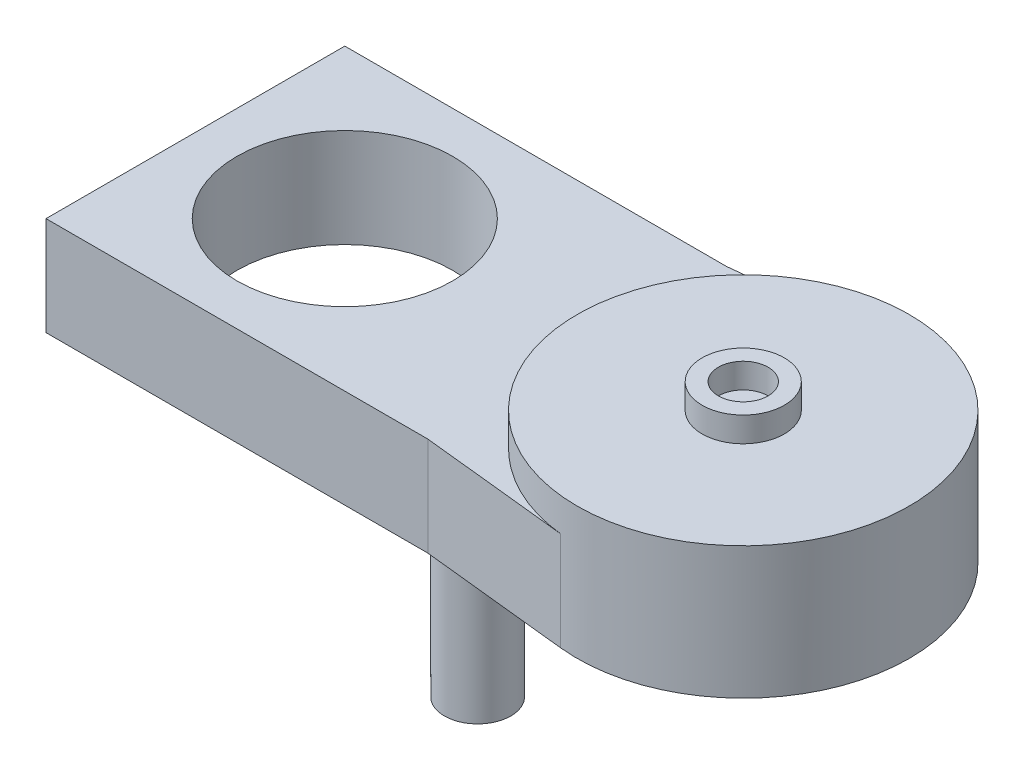
SolidWorks part; units mm, degrees
ref_plane "Front Plane" through (0, 0, 0) normal (0, 0, 1) x (1, 0, 0)
ref_plane "Top Plane" through (0, 0, 0) normal (0, 1, 0) x (1, 0, 0)
ref_plane "Right Plane" through (0, 0, 0) normal (1, 0, 0) x (0, 0, -1)
sketch "Sketch1" plane through (0, 0, 0) normal (0, 1, 0) x (1, 0, 0)
  line L0 (-36.0976, 0) -> (47.5883, 0) construction
  line L1 (14, 9) -> (22.9503, 9.9448)
  line L2 (-9, -9) -> (9, -9)
  line L3 (-9, -9) -> (-9, 9)
  line L4 (-9, 9) -> (9, 9)
  line L6 (-9, -9) -> (9, 9) construction
  line L7 (-9, 9) -> (9, -9) construction
  line L8 (9, -9) -> (14, -9)
  line L10 (9, 9) -> (14, 9)
  line L12 (9, -9) -> (14, 9) construction
  line L13 (9, 9) -> (14, -9) construction
  line L14 (14, -9) -> (22.9503, -9.9448)
  circle A0 centre (0, 0) radius 6.5
  arc A1 (22.9503, -9.9448) -> (22.9503, 9.9448) centre (24, 0) ccw
  point P3 (0, 0)
  point P10 (11.5, 0)
  dimension "D3" = 13
  dimension "D6" = 20
  dimension "D1" = 18
  dimension "D2" = 18
  dimension "D4" = 5
  dimension "D5" = 18
extrude "Boss-Extrude2" add sketch "Sketch1" along normal blind 5.95
sketch "Sketch3" plane through (0, 5.95, 0) normal (0, 1, 0) x (1, 0, 0)
  line L0 (-10.9363, 0) -> (39.1113, 0) construction
  circle A0 centre (24, 0) radius 10
  arc A1 (22.9503, -9.9448) -> (22.9503, 9.9448) centre (24, 0) ccw construction
  dimension "D1" = 20
extrude "Boss-Extrude3" add sketch "Sketch3" along normal blind 2
sketch "Sketch4" plane through (0, 0, 0) normal (0, -1, 0) x (1, 0, 0)
  line L0 (9, 9) -> (9, -9) construction
  line L1 (-9, 9) -> (14, 9) construction
  line L2 (14, -9) -> (-9, -9) construction
  line L3 (14, 9) -> (14, -9) construction
  line L4 (13, 9) -> (13, -9) construction
  line L5 (-10.2489, 0) -> (36.2964, 0) construction
  circle A0 centre (13, 5) radius 2
  circle A1 centre (13, -5) radius 2
  dimension "D3" = 4
  dimension "D1" = 18
  dimension "D2" = 4
  dimension "D4" = 4
extrude "Boss-Extrude4" add sketch "Sketch4" along normal blind 10
sketch "Sketch5" plane through (0, 7.95, 0) normal (0, 1, 0) x (1, 0, 0)
  line L0 (-11.9183, 0) -> (37.2129, 0) construction
  line L1 (24, 10) -> (24, -10) construction
  circle A0 centre (24, 0) radius 10 construction
  circle A1 centre (24, 0) radius 1.5
  circle A2 centre (24, 0) radius 2.475
  dimension "D1" = 3
  dimension "D2" = 4.95
extrude "Boss-Extrude5" add sketch "Sketch5" along normal blind 1.5
